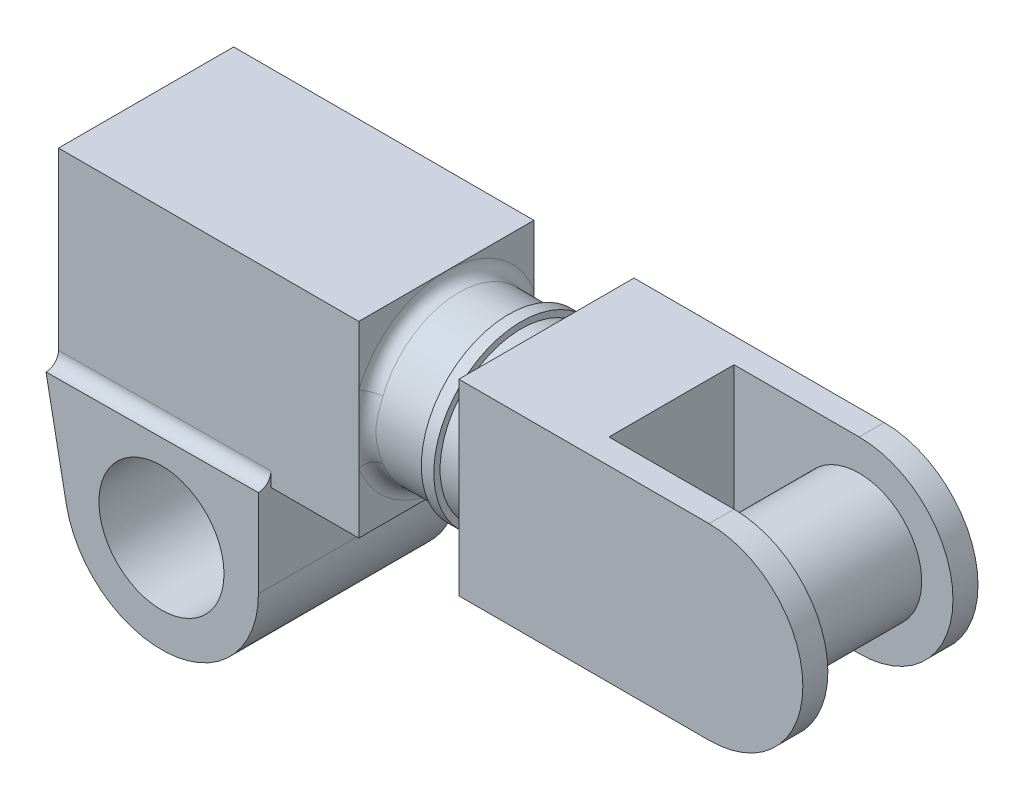
SolidWorks part; units mm, degrees
ref_plane "Front Plane" through (0, 0, 0) normal (0, 0, 1) x (1, 0, 0)
ref_plane "Top Plane" through (0, 0, 0) normal (0, 1, 0) x (1, 0, 0)
ref_plane "Right Plane" through (0, 0, 0) normal (1, 0, 0) x (0, 0, -1)
sketch "Sketch1" plane through (0, 0, 0) normal (1, 0, 0) x (0, 0, -1)
  line L1 (1778, -1905) -> (-1778, -1905)
  line L2 (1778, -1905) -> (1778, 1905)
  line L3 (1778, 1905) -> (-1778, 1905)
  line L4 (-1778, -1905) -> (-1778, 1905)
  line L5 (1778, -1905) -> (-1778, 1905) construction
  line L6 (1778, 1905) -> (-1778, -1905) construction
  point P0 (0, 0)
  dimension "D1" = 3810
  dimension "D2" = 3556
extrude "Boss-Extrude1" add sketch "Sketch1" along normal blind 6096
sketch "Sketch2" plane through (6096, 0, 0) normal (1, 0, 0) x (0, 0, -1)
  circle A0 centre (0, 0) radius 1651
  dimension "D1" = 3302
extrude "Boss-Extrude2" add sketch "Sketch2" along normal blind 1270
sketch "Sketch3" plane through (7366, 0, 0) normal (1, 0, 0) x (0, 0, -1)
  circle A0 centre (0, 0) radius 1778
  dimension "D1" = 3556
extrude "Boss-Extrude3" add sketch "Sketch3" along normal blind 254
sketch "Sketch4" plane through (0, 0, 0) normal (0, 0, 1) x (1, 0, 0)
  line L0 (0, -1905) -> (411.9566, -4024.3331)
  line L1 (0, 1905) -> (0, -1905) construction
  line L2 (4312.7897, -3648.7256) -> (4312.7897, -1870.7256)
  line L4 (0, -1905) -> (4312.7897, -1870.7256)
  arc A0 (411.9566, -4024.3331) -> (4312.7897, -3648.7256) centre (2344.2897, -3648.7256) ccw
  circle A1 centre (2344.2897, -3648.7256) radius 1270
  dimension "D1" = 3937
  dimension "D2" = 2540
  dimension "D3" = 191
  dimension "D4" = 2159
  dimension "D5" = 2159
  dimension "D6" = 1778
extrude "Boss-Extrude4" add sketch "Sketch4" along normal mid plane 4064
fillet "Fillet1" radius 254 3 edges at (2156.3949, -1887.8628, -1778) (6096, 0, -1651) (2156.3949, -1887.8628, 1778)
sketch "Sketch5" plane through (7620, 0, 0) normal (1, 0, 0) x (0, 0, -1)
  circle A0 centre (0, 0) radius 1651
  dimension "D1" = 3302
extrude "Boss-Extrude5" add sketch "Sketch5" along normal blind 508
sketch "Sketch6" plane through (0, 0, 0) normal (0, 0, 1) x (1, 0, 0)
  line L0 (13208, 1905) -> (8128, 1905)
  line L1 (8128, 1905) -> (8128, -1905)
  line L2 (8128, -1905) -> (13208, -1905)
  line L3 (8128, -1651) -> (8128, 1651) construction
  arc A0 (13208, -1905) -> (13208, 1905) centre (13208, 0) ccw
  dimension "D1" = 3810
  dimension "D2" = 5080
extrude "Boss-Extrude6" add sketch "Sketch6" along normal mid plane 3556
sketch "Sketch7" plane through (0, 0, 0) normal (0, 0, 1) x (1, 0, 0)
  line L0 (13208, 1905) -> (10668, 1905)
  line L1 (13208, 1905) -> (8128, 1905) construction
  line L2 (10668, 1905) -> (10668, -1905)
  line L3 (8128, -1905) -> (13208, -1905) construction
  line L4 (10668, -1905) -> (13208, -1905)
  arc A0 (13208, -1905) -> (13208, 1905) centre (13208, 0) ccw construction
  arc A1 (13208, -1905) -> (13208, 1905) centre (13208, 0) ccw
extrude "Cut-Extrude1" cut sketch "Sketch7" against normal mid plane 2540
sketch "Sketch8" plane through (0, 0, -1270) normal (0, 0, 1) x (1, 0, 0)
  circle A0 centre (13208, 0) radius 1270
  dimension "D1" = 2540
extrude "Boss-Extrude7" add sketch "Sketch8" along normal blind 2540
